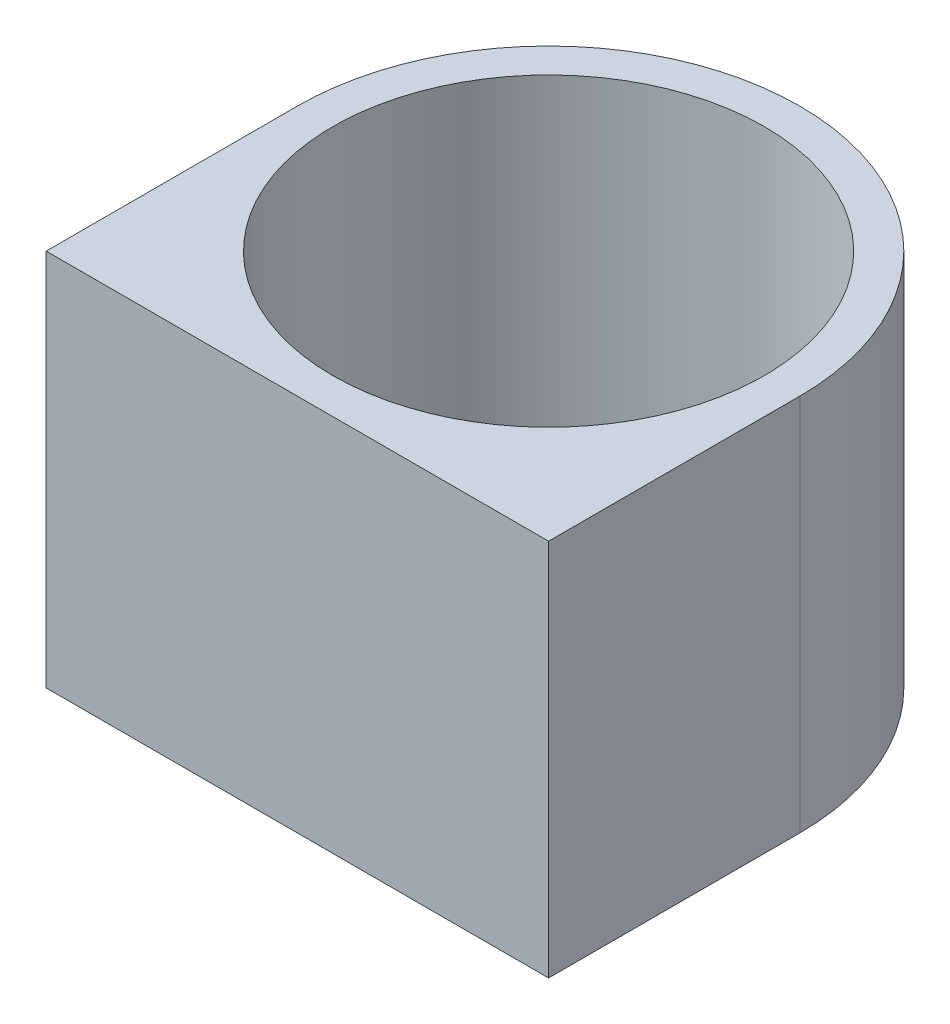
SolidWorks part; units mm, degrees
ref_plane "Front Plane" through (0, 0, 0) normal (0, 0, 1) x (1, 0, 0)
ref_plane "Top Plane" through (0, 0, 0) normal (0, 1, 0) x (1, 0, 0)
ref_plane "Right Plane" through (0, 0, 0) normal (1, 0, 0) x (0, 0, -1)
sketch "Sketch1" plane through (0, 0, 0) normal (0, 1, 0) x (1, 0, 0)
  circle A0 centre (0, 0) radius 18.25
  circle A1 centre (0, 0) radius 11.5
  circle A2 centre (0, 0) radius 14 construction
  circle A3 centre (0, 14) radius 1.6
  circle A4 centre (14, 0) radius 1.6
  circle A5 centre (0, -14) radius 1.6
  circle A6 centre (-14, 0) radius 1.6
  circle A7 centre (0, 0) radius 21.25
  point P16 (0, 0)
  dimension "D1" = 36.5
  dimension "D2" = 23
  dimension "D3" = 28
  dimension "D4" = 3.2
  dimension "D6" = 3
  dimension "D5" = 4
extrude "Boss-Extrude1" add sketch "Sketch1" along normal blind 2 contours A0 A6 A5 A4 A3 A1 region at (-17.7338, 0, 0)
extrude "Boss-Extrude2" add sketch "Sketch1<3>" along normal blind 32 contours A7 A0 region at (-20.649, 0, 0)
sketch "Sketch1<3>" plane through (0, 0, 0) normal (0, 1, 0) x (1, 0, 0) same geometry as "Sketch1"
sketch "Sketch2" plane through (0, 0, 0) normal (0, 1, 0) x (1, 0, 0)
  line L0 (-21.25, 0) -> (-21.25, -21.25)
  line L1 (-21.25, -21.25) -> (21.25, -21.25)
  line L2 (21.25, -21.25) -> (21.25, 0)
  circle A0 centre (0, 0) radius 21.25 construction
  circle A1 centre (0, 0) radius 21.25
extrude "Boss-Extrude3" add sketch "Sketch2" along normal blind 32 contours A1 L0 L1 | A1 L1 L2 region at (-16.5034, 0, 16.5034) region at (16.5034, 0, 16.5034)
